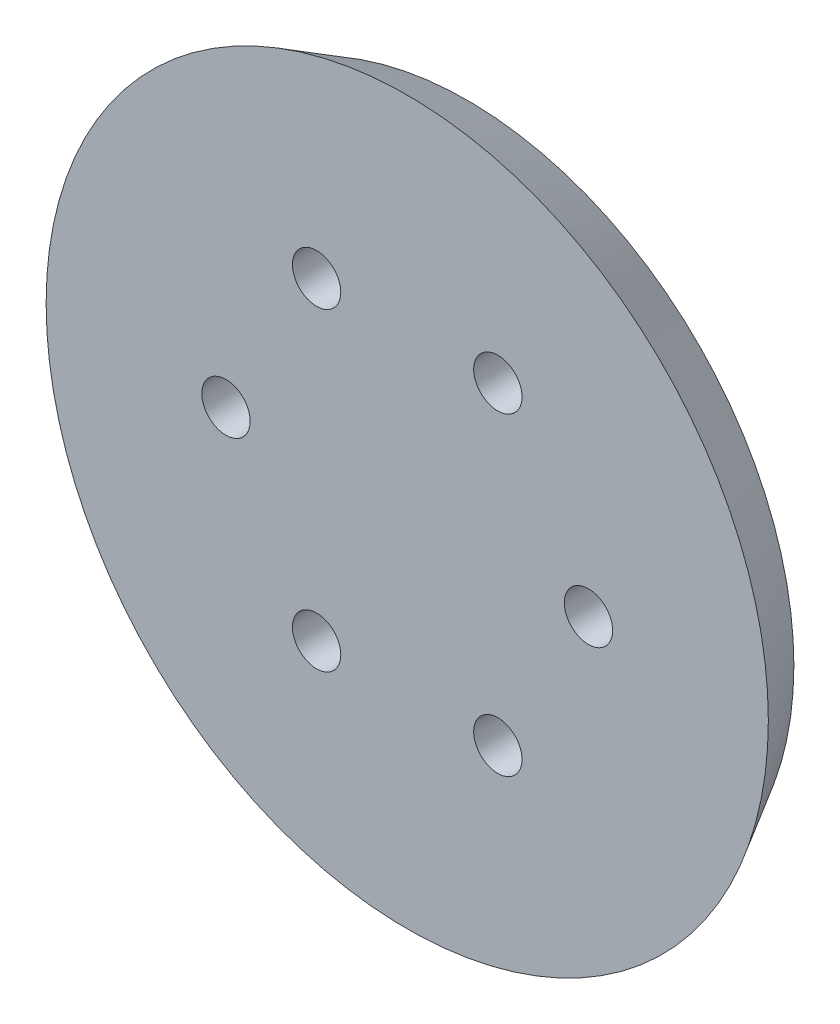
SolidWorks part; units mm, degrees
material "Polyurethane Foam Rigid"
ref_plane "Front Plane" through (0, 0, 0) normal (0, 0, 1) x (1, 0, 0)
ref_plane "Top Plane" through (0, 0, 0) normal (0, 1, 0) x (1, 0, 0)
ref_plane "Right Plane" through (0, 0, 0) normal (1, 0, 0) x (0, 0, -1)
sketch "Sketch1" plane through (0, 0, 0) normal (0, 0, 1) x (1, 0, 0)
  circle A0 centre (0, 0) radius 76.2
  circle A1 centre (0, 0) radius 38.1 construction
  circle A2 centre (38.1, 0) radius 5.08
  circle A3 centre (19.05, -32.9956) radius 5.08
  circle A4 centre (-19.05, -32.9956) radius 5.08
  circle A5 centre (-38.1, 0) radius 5.08
  circle A6 centre (-19.05, 32.9956) radius 5.08
  circle A7 centre (19.05, 32.9956) radius 5.08
  point P19 (0, 0)
  dimension "D1" = 6
extrude "Boss-Extrude1" add sketch "Sketch1" along normal blind 12.7
chamfer "Chamfer1" distance 7.62 angle 60 1 edges at (76.2, 0, 0) first distance on face at (-13.97, 32.9956, 0)
sketch "Sketch3" plane through (0, 0, 0) normal (0, 0, -1) x (-1, 0, 0)
  circle A0 centre (0, 0) radius 5.08
extrude "Boss-Extrude2" add sketch "Sketch3" along normal blind 2.54
sketch "Sketch4" plane through (0, 0, -2.54) normal (0, 0, -1) x (-1, 0, 0)
  circle A0 centre (0, 0) radius 4.064
extrude "Boss-Extrude3" add sketch "Sketch4" along normal blind 1.27
sketch "Sketch5" plane through (0, 0, -3.81) normal (0, 0, -1) x (-1, 0, 0)
  circle A0 centre (0, 0) radius 4.572
extrude "Boss-Extrude4" add sketch "Sketch5" along normal blind 6.35
ref_plane "Plane2" through (0, 0, -9.9568) normal (0, 0, -1) x (-1, 0, 0)
sketch "Sketch6" plane through (0, 0, -9.9568) normal (0, 0, -1) x (-1, 0, 0)
  circle A0 centre (0, 0) radius 4.572 construction
  circle A1 centre (0, 0) radius 4.572
curve "Helix/Spiral1" pitch 1.27 height 7.62 turns 6
sketch "Sketch8" plane through (0, 0, 0) normal (1, 0, 0) x (0, 0, -1)
  circle A0 centre (20.08, 4.7379) radius 0.254
